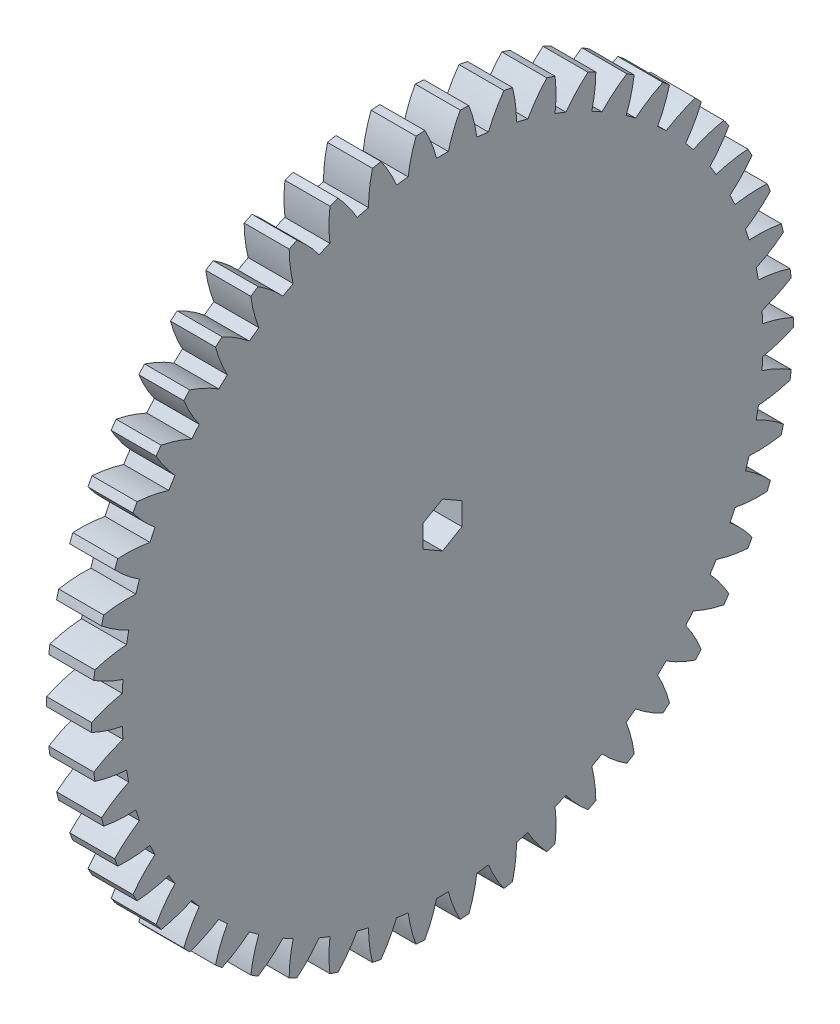
SolidWorks part; units mm, degrees
ref_plane "Plane1" through (0, 0, 0) normal (0, 0, 1) x (1, 0, 0)
ref_plane "Plane2" through (0, 0, 0) normal (0, 1, 0) x (1, 0, 0)
ref_plane "Plane3" through (0, 0, 0) normal (1, 0, 0) x (0, 0, -1)
sketch "HoldingSke" plane through (0, 0, 0) normal (0, 1, 0) x (1, 0, 0)
  line L0 (0, 0) -> (0.4285, -0.5107)
  line L1 (-15, 0) -> (100, 0) construction
  line L2 (0, 0) -> (-2.1039, 2.3779)
  line L3 (0, 0) -> (-11.863, 4.5341)
  line L4 (0, 0) -> (5.5511, 6.6156)
  line L5 (0, 0) -> (-46.8476, -17.4728)
  line L6 (0, 0) -> (-4.1448, -2.7965)
  line L7 (-2.1039, 2.3779) -> (8.6586, 51.2059)
  line L8 (-76.2, 54.61) -> (-75.3, 54.61)
  line L9 (-71.009, 38.7566) -> (-53.1078, 45.2721)
  line L10 (-76.2, 71.12) -> (104.1128, 71.12)
  line L11 (0, 0) -> (-5, 0)
  line L12 (-76.2, 101.6) -> (-76.147, 101.6)
  line L13 (24.9733, 27.94) -> (52.9518, 28.4284)
  line L14 (24.9733, 27.94) -> (24.9743, 27.94)
  line L15 (24.9733, 27.94) -> (100.4006, 29.5858)
  line L16 (-63.627, -1.5) -> (-12.827, -1.5)
  circle A0 centre (0, 0) radius 2.5
  circle A1 centre (0, 0) radius 35.624
  circle A2 centre (0, 0) radius 37.5
  circle A3 centre (0, 0) radius 2.5
  dimension "MHD" = 71.248
  dimension "Hub_dia" = 75
  dimension "Bore" = 5
  dimension "MBD" = 5
  dimension "Num_teeth" = 50
  dimension "Pitch" = 0.6667
  dimension "Overall_len" = 50
  dimension "Show_teeth" = 50
  dimension "Thickness" = 5
  dimension "OAL" = 50.0001
  dimension "T_dim" = 0.9
  dimension "Ap" = 20
  dimension "H" = 19.05
  dimension "Pitch_radius" = 180.3128
  dimension "Width" = 5
  dimension "Backlash" = 0.053
  dimension "Addendum_fac" = 1
  dimension "Dedendum_fac" = 1.25
  dimension "Clearance_fac" = 0.25
  dimension "Dedendum_add" = 0.001
  dimension "Module" = 1.5
sketch "BasProSke" plane through (0, 0, 0) normal (0, 1, 0) x (1, 0, 0)
  line L0 (-10, 0) -> (60, 0) construction
  line L1 (0, 0) -> (0, 39)
  line L2 (0, 0) -> (5, 0)
  line L3 (5, 0) -> (5, 39)
  line L4 (5, 39) -> (0, 39)
  dimension "Thickness" = 5
  dimension "Diameter" = 78
revolve "Base-Revolve" add sketch "BasProSke" angle 360 about L0
sketch "TooCutSke" plane through (0, 0, 0) normal (1, 0, 0) x (0, 0, -1)
  line L1 (0, 0) -> (0, 107) construction
  line L2 (0, 0) -> (-1.2706, 37.4785) construction
  line L3 (0, 0) -> (-4.7073, 74.8207) construction
  line L4 (-1.2706, 37.4785) -> (-2.3537, 37.4103) construction
  arc A0 (0.65, 35.6181) -> (-0.65, 35.6181) centre (0, 0) ccw
  arc A1 (1.9801, 38.9751) -> (-1.9801, 38.9751) centre (0, 0) ccw
  circle A2 centre (0, 0) radius 37.5 construction
  circle A3 centre (0, 0) radius 35.2385 construction
  arc A4 (-0.65, 35.6181) -> (-1.9801, 38.9751) centre (-15.1589, 31.8113) ccw
  arc A5 (1.9801, 38.9751) -> (0.65, 35.6181) centre (15.1589, 31.8113) ccw
  dimension "Root_dia" = 71.248
  dimension "Overcut_dia" = 78.0508
  dimension "Pitch_dia" = 75
  dimension "Base_dia" = 70.4769
  dimension "Flank_rad" = 15
  dimension "Half_ang" = 3.6
  dimension "Half_CT" = 1.0852
extrude "ToothCut" cut sketch "TooCutSke" along normal through all
fillet "Breaks" [suppressed] radius 0.03 tangent propagation no
fillet "RootFillets" [suppressed] radius 0.376
pattern_circular "TeethCuts" count 50 every 7.2 about axis through (-10, 0, 0) along (1, 0, 0) of "ToothCut", "RootFillets", "Breaks"
sketch "HubNeaOneSke" plane through (0, 0, 0) normal (-1, 0, 0) x (0, 0, 1)
  circle A0 centre (0, 0) radius 35.624
  dimension "Diameter" = 71.248
extrude "HubNearOne" [suppressed] add sketch "HubNeaOneSke" along normal blind 45.0001
sketch "HubNeaBotSke" plane through (0, 0, 0) normal (-1, 0, 0) x (0, 0, 1)
  circle A0 centre (0, 0) radius 35.624
  dimension "Diameter" = 71.248
extrude "HubNearBoth" [suppressed] add sketch "HubNeaBotSke" along normal blind 22.5
ref_plane "FarPln" through (5, 0, 0) normal (1, 0, 0) x (0, 0, -1)
sketch "HubFarSke" plane through (5, 0, 0) normal (1, 0, 0) x (0, 0, -1)
  circle A0 centre (0, 0) radius 35.624
  dimension "Diameter" = 71.248
extrude "HubFar" [suppressed] add sketch "HubFarSke" along normal blind 22.5
sketch "BorSke" plane through (0, 0, 0) normal (1, 0, 0) x (0, 0, -1)
  line L1 (0, -2.5) -> (2.1651, -1.25)
  line L2 (2.1651, -1.25) -> (2.1651, 1.25)
  line L3 (2.1651, 1.25) -> (0, 2.5)
  line L4 (0, 2.5) -> (-2.1651, 1.25)
  line L5 (-2.1651, 1.25) -> (-2.1651, -1.25)
  line L6 (-2.1651, -1.25) -> (0, -2.5)
  circle A0 centre (0, 0) radius 2.5 construction
  circle A1 centre (0, 0) radius 2.1651 construction
  dimension "Diameter" = 5
extrude "Bore" cut sketch "BorSke" along normal mid plane 100.0001
sketch "KeySke" plane through (0, 0, 0) normal (1, 0, 0) x (0, 0, -1)
  line L0 (-1, 0) -> (-1, 3.4)
  line L1 (-1, 3.4) -> (1, 3.4)
  line L2 (1, 3.4) -> (1, 0)
  line L3 (0, 0) -> (0, 34) construction
  line L4 (-1, 0) -> (1, 0)
  dimension "Offset" = 3.4
  dimension "Width" = 2
extrude "Keyway" [suppressed] cut sketch "KeySke" along normal mid plane 100.0001
pattern_circular "Keyway2" [suppressed] count 2 every 90 about axis through (-10, 0, 0) along (1, 0, 0) reverse direction yes
sketch "Sketch1" plane through (0, 0, 0) normal (-1, 0, 0) x (0, 0, 1)
  line L12 (2.1651, -1.25) -> (2.1651, 1.25) construction
  line L13 (2.1651, 1.25) -> (0, 2.5) construction
  line L14 (0, 2.5) -> (-2.1651, 1.25) construction
  line L15 (-2.1651, 1.25) -> (-2.1651, -1.25) construction
  line L16 (-2.1651, -1.25) -> (0, -2.5) construction
  line L17 (0, -2.5) -> (2.1651, -1.25) construction
  line L18 (2.1651, -1.25) -> (2.1651, 1.25)
  line L19 (2.1651, 1.25) -> (0, 2.5)
  line L20 (0, 2.5) -> (-2.1651, 1.25)
  line L21 (-2.1651, 1.25) -> (-2.1651, -1.25)
  line L22 (-2.1651, -1.25) -> (0, -2.5)
  line L23 (0, -2.5) -> (2.1651, -1.25)
  line L24 (4.5499, -3.3057) -> (-4.5499, 3.3057) construction
  arc A40 (0.1868, -8.9981) -> (0.8757, -5.5554) centre (-1.8542, -6.7994) ccw
  arc A41 (-0.1868, -8.9981) -> (0.1868, -8.9981) centre (0, 0) ccw
  arc A42 (-0.8757, -5.5554) -> (-0.1868, -8.9981) centre (1.8542, -6.7994) ccw
  arc A43 (-2.5569, -5.0091) -> (-0.8757, -5.5554) centre (0, 0) ccw
  arc A44 (-5.1378, -7.3894) -> (-2.5569, -5.0091) centre (-5.4967, -4.4109) ccw
  arc A45 (-5.4401, -7.1698) -> (-5.1378, -7.3894) centre (0, 0) ccw
  arc A46 (-3.9738, -3.9797) -> (-5.4401, -7.1698) centre (-2.4965, -6.5907) ccw
  arc A47 (-5.0129, -2.5496) -> (-3.9738, -3.9797) centre (0, 0) ccw
  arc A48 (-8.4999, -2.9582) -> (-5.0129, -2.5496) centre (-7.0396, -0.3377) ccw
  arc A49 (-8.6154, -2.6029) -> (-8.4999, -2.9582) centre (0, 0) ccw
  arc A50 (-5.5541, -0.8839) -> (-8.6154, -2.6029) centre (-5.8936, -3.8646) ccw
  arc A51 (-5.5541, 0.8839) -> (-5.5541, -0.8839) centre (0, 0) ccw
  arc A52 (-8.6154, 2.6029) -> (-5.5541, 0.8839) centre (-5.8936, 3.8646) ccw
  arc A53 (-8.4999, 2.9582) -> (-8.6154, 2.6029) centre (0, 0) ccw
  arc A54 (-5.0129, 2.5496) -> (-8.4999, 2.9582) centre (-7.0396, 0.3377) ccw
  arc A55 (-3.9738, 3.9797) -> (-5.0129, 2.5496) centre (0, 0) ccw
  arc A56 (-5.4401, 7.1698) -> (-3.9738, 3.9797) centre (-2.4965, 6.5907) ccw
  arc A57 (-5.1378, 7.3894) -> (-5.4401, 7.1698) centre (0, 0) ccw
  arc A58 (-2.5569, 5.0091) -> (-5.1378, 7.3894) centre (-5.4967, 4.4109) ccw
  arc A59 (-0.8757, 5.5554) -> (-2.5569, 5.0091) centre (0, 0) ccw
  arc A60 (-0.1868, 8.9981) -> (-0.8757, 5.5554) centre (1.8542, 6.7994) ccw
  arc A61 (0.1868, 8.9981) -> (-0.1868, 8.9981) centre (0, 0) ccw
  arc A62 (0.8757, 5.5554) -> (0.1868, 8.9981) centre (-1.8542, 6.7994) ccw
  arc A63 (2.5569, 5.0091) -> (0.8757, 5.5554) centre (0, 0) ccw
  arc A64 (5.1378, 7.3894) -> (2.5569, 5.0091) centre (5.4967, 4.4109) ccw
  arc A65 (5.4401, 7.1698) -> (5.1378, 7.3894) centre (0, 0) ccw
  arc A66 (3.9738, 3.9797) -> (5.4401, 7.1698) centre (2.4965, 6.5907) ccw
  arc A67 (5.0129, 2.5496) -> (3.9738, 3.9797) centre (0, 0) ccw
  arc A68 (8.4999, 2.9582) -> (5.0129, 2.5496) centre (7.0396, 0.3377) ccw
  arc A69 (8.6154, 2.6029) -> (8.4999, 2.9582) centre (0, 0) ccw
  arc A70 (5.5541, 0.8839) -> (8.6154, 2.6029) centre (5.8936, 3.8646) ccw
  arc A71 (5.5541, -0.8839) -> (5.5541, 0.8839) centre (0, 0) ccw
  arc A72 (8.6154, -2.6029) -> (5.5541, -0.8839) centre (5.8936, -3.8646) ccw
  arc A73 (8.4999, -2.9582) -> (8.6154, -2.6029) centre (0, 0) ccw
  arc A74 (5.0129, -2.5496) -> (8.4999, -2.9582) centre (7.0396, -0.3377) ccw
  arc A75 (3.9738, -3.9797) -> (5.0129, -2.5496) centre (0, 0) ccw
  arc A76 (5.4401, -7.1698) -> (3.9738, -3.9797) centre (2.4965, -6.5907) ccw
  arc A77 (5.1378, -7.3894) -> (5.4401, -7.1698) centre (0, 0) ccw
  arc A78 (2.5569, -5.0091) -> (5.1378, -7.3894) centre (5.4967, -4.4109) ccw
  arc A79 (0.8757, -5.5554) -> (2.5569, -5.0091) centre (0, 0) ccw
extrude "Boss-Extrude1" add sketch "Sketch1" along normal blind 10
equation "' \"Module@HoldingSke\" = 6.35"
equation "' \"Num_teeth@HoldingSke\" = 12"
equation "' \"Ap@HoldingSke\" =  20"
equation "' \"Ap@HoldingSke\" = 20"
equation "' \"Width@HoldingSke\" = 0.5 * 25.4"
equation "' \"Hub_dia@HoldingSke\"= 1 * 25.4"
equation "' \"Hub_dia@HoldingSke\" = 1 * 25.4"
equation "' \"Overall_len@HoldingSke\" = 1.0 * 25.4"
equation "' \"Bore@HoldingSke\" = 0.75 * 25.4"
equation "' \"T_dim@HoldingSke\" = 0.1 * 25.4"
equation "' \"Width@KeySke\" = 0.25 * 25.4"
equation "' \"Show_teeth@HoldingSke\" = 13"
equation "' \"Backlash@HoldingSke\" = 0.009 * 25.4"
equation "' \"Addendum_fac@HoldingSke\" = 1.0"
equation "' \"Dedendum_fac@HoldingSke\" = 1.25"
equation "' \"Dedendum_add@HoldingSke\" = 0.00005 * 25.4"
equation "' \"Clearance_fac@HoldingSke\" = 0.25"
equation "\"Pitch@HoldingSke\" = 1 / \"Module@HoldingSke\""
equation "\"Overcut_dia@TooCutSke\" = (\"Num_teeth@HoldingSke\" + 2 * \"Addendum_fac@HoldingSke\") / \"Pitch@HoldingSke\" + 0.002 * 25.4"
equation "\"Pitch_dia@TooCutSke\" = \"Num_teeth@HoldingSke\" / \"Pitch@HoldingSke\""
equation "\"Base_dia@TooCutSke\" = \"Num_teeth@HoldingSke\" / \"Pitch@HoldingSke\" * cos((\"Ap@HoldingSke\"  * 3.14159265 / 180))"
equation "\"Root_dia@TooCutSke\" = (\"Num_teeth@HoldingSke\" + 2) / \"Pitch@HoldingSke\" - 2 * (\"Addendum_fac@HoldingSke\" + \"Dedendum_fac@HoldingSke\") / \"Pitch@HoldingSke\" - \"Dedendum_add@HoldingSke\" * 2"
equation "\"Half_ang@TooCutSke\" = 180 / \"Num_teeth@HoldingSke\""
equation "\"Half_CT@TooCutSke\" = \"Num_teeth@HoldingSke\" / \"Pitch@HoldingSke\" * sin((3.14159265 / 2 / \"Num_teeth@HoldingSke\")) / 2 - 7 * \"Backlash@HoldingSke\" / 4"
equation "\"Flank_rad@TooCutSke\" = \"Num_teeth@HoldingSke\" / \"Pitch@HoldingSke\" / 5"
equation "\"Radius@RootFillets\" = \"Clearance_fac@HoldingSke\" / \"Pitch@HoldingSke\" + \"Dedendum_add@HoldingSke\""
equation "\"Break_rad@Breaks\" = 0.02 / \"Pitch@HoldingSke\""
equation "\"Thickness@HoldingSke\" = \"Width@HoldingSke\""
equation "\"OAL@HoldingSke\" = \"Thickness@HoldingSke\""
equation "\"MHD@HoldingSke\" = (\"Num_teeth@HoldingSke\" + 2) / \"Pitch@HoldingSke\" - 2 * (\"Addendum_fac@HoldingSke\" + \"Dedendum_fac@HoldingSke\")  / \"Pitch@HoldingSke\" - \"Dedendum_add@HoldingSke\" * 2"
equation "\"MBD@HoldingSke\" = (\"Num_teeth@HoldingSke\" + 2) / \"Pitch@HoldingSke\" - 2 * (\"Addendum_fac@HoldingSke\" + \"Dedendum_fac@HoldingSke\")  / \"Pitch@HoldingSke\" - \"Dedendum_add@HoldingSke\" * 2 - 0.002 * 25.4"
equation "\"MHD@HoldingSke\" = ((sgn( \"MHD@HoldingSke\" - \"Hub_dia@HoldingSke\" )-1)*( \"MHD@HoldingSke\" - \"Hub_dia@HoldingSke\" ))/-2+ \"Hub_dia@HoldingSke\""
equation "\"MBD@HoldingSke\" = ((sgn( \"MBD@HoldingSke\" - \"Bore@HoldingSke\" )-1)*( \"MBD@HoldingSke\" - \"Bore@HoldingSke\" ))/-2+ \"Bore@HoldingSke\""
equation "\"OAL@HoldingSke\" = ((sgn( \"OAL@HoldingSke\" - \"Overall_len@HoldingSke\" )+1)*( \"OAL@HoldingSke\" - \"Overall_len@HoldingSke\" ))/2 + \"Overall_len@HoldingSke\" + 0.000002 * 25.4"
equation "\"Num_teeth@TeethCuts\" = int( \"Show_teeth@HoldingSke\" ) + 1"
equation "\"Num_teeth@TeethCuts\" = ((sgn( \"Num_teeth@TeethCuts\" - \"Num_teeth@HoldingSke\" )-1)*( \"Num_teeth@TeethCuts\" - \"Num_teeth@HoldingSke\" ))/-2+ \"Num_teeth@HoldingSke\""
equation "\"Num_teeth@TeethCuts\" = ((sgn( \"Num_teeth@TeethCuts\" - 2.0)+1)*( \"Num_teeth@TeethCuts\" - 2.0))/2 +2.0"
equation "\"Angle@TeethCuts\" = 360.0 / \"Num_teeth@HoldingSke\""
equation "\"Diameter@BasProSke\" = (\"Num_teeth@HoldingSke\" + 2 * \"Addendum_fac@HoldingSke\") / \"Pitch@HoldingSke\""
equation "\"Thickness@BasProSke\"  = \"Thickness@HoldingSke\""
equation "' \"Fillet_rad@BasProSke\" =  \"Thickness@HoldingSke\" * 0.05"
equation "' \"Fillet_rad@BasProSke\" = \"Thickness@HoldingSke\" * 0.05"
equation "\"MHD@HoldingSke\" = ((sgn( \"MHD@HoldingSke\" - \"Root_dia@TooCutSke\" )-1)*( \"MHD@HoldingSke\" - \"Root_dia@TooCutSke\" ))/-2+ \"Root_dia@TooCutSke\""
equation "\"Diameter@HubNeaOneSke\" = \"MHD@HoldingSke\""
equation "\"Length@HubNearOne\" = \"OAL@HoldingSke\" - \"Thickness@BasProSke\""
equation "\"Diameter@HubNeaBotSke\" = \"MHD@HoldingSke\""
equation "\"Length@HubNearBoth\" = ( \"OAL@HoldingSke\" - \"Thickness@BasProSke\" ) / 2.0"
equation "\"Thickness@FarPln\" = \"Thickness@BasProSke\""
equation "\"Diameter@HubFarSke\" = \"MHD@HoldingSke\""
equation "\"Length@HubFar\" = ( \"OAL@HoldingSke\" - \"Thickness@BasProSke\" ) / 2.0"
equation "\"Diameter@BorSke\" = \"MBD@HoldingSke\""
equation "\"D1@Bore\" = \"OAL@HoldingSke\" * 2.0"
equation "\"D1@Keyway\" = \"OAL@HoldingSke\" * 2.0"
equation "\"Offset@KeySke\" = \"T_dim@HoldingSke\" + \"MBD@HoldingSke\" / 2.0"
